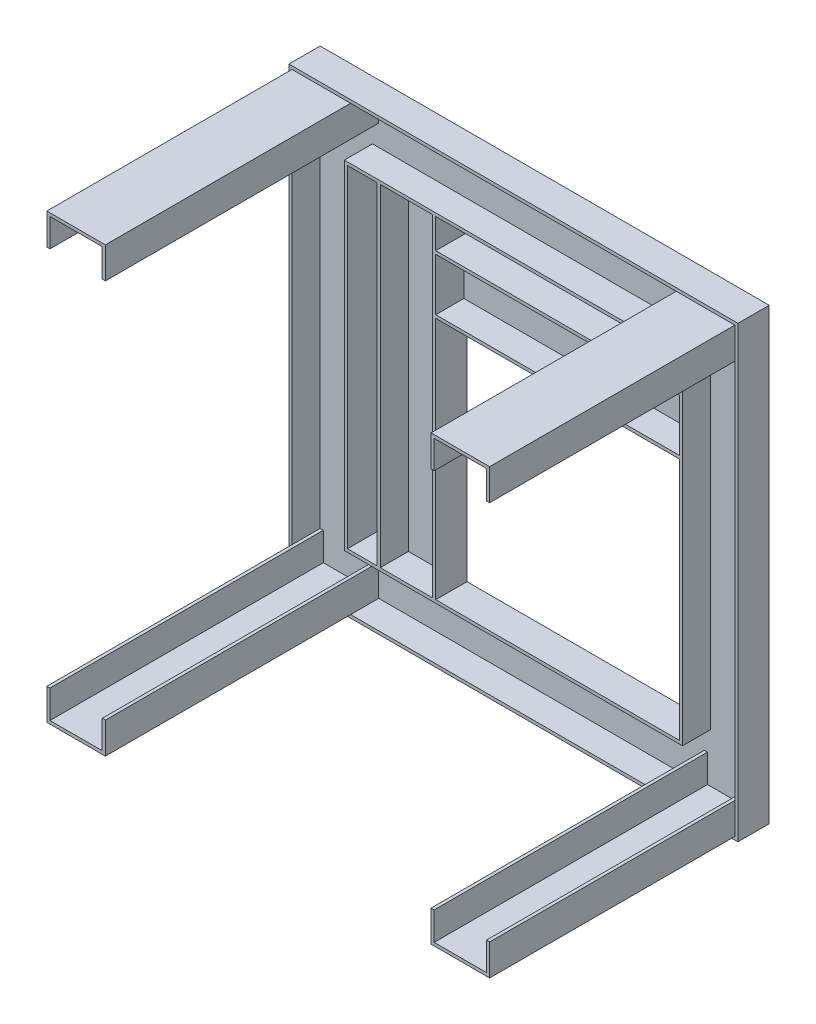
SolidWorks part; units mm, degrees
ref_plane "Front Plane" through (0, 0, 0) normal (0, 0, 1) x (1, 0, 0)
ref_plane "Top Plane" through (0, 0, 0) normal (0, 1, 0) x (1, 0, 0)
ref_plane "Right Plane" through (0, 0, 0) normal (1, 0, 0) x (0, 0, -1)
sketch "Sketch1" plane through (0, 0, 0) normal (0, 0, 1) x (1, 0, 0)
  line L1 (-250, -250) -> (250, -250)
  line L2 (-250, -250) -> (-250, 250)
  line L3 (-250, 250) -> (250, 250)
  line L4 (250, -250) -> (250, 250)
  line L5 (-250, -250) -> (250, 250) construction
  line L6 (-250, 250) -> (250, -250) construction
  point P0 (0, 0)
  dimension "D1" = 500
ref_plane "Plane1" through (0, -250, 0) normal (0, 1, 0) x (1, 0, 0)
sketch "Sketch2" plane through (0, -250, 0) normal (0, 1, 0) x (1, 0, 0)
  line L0 (250, 2) -> (250, -2) construction
  line L1 (212.5, 2) -> (287.5, 2)
  line L2 (287.5, 2) -> (287.5, -38)
  line L3 (287.5, -38) -> (283.5, -38)
  line L4 (283.5, -38) -> (283.5, -2)
  line L5 (283.5, -2) -> (216.5, -2)
  line L6 (-250, 0) -> (250, 0) construction
  line L7 (212.5, -38) -> (216.5, -38)
  line L8 (216.5, -38) -> (216.5, -2)
  line L9 (212.5, 2) -> (212.5, -38)
  point P13 (250, -2)
  dimension "D1" = 37.5
  dimension "D2" = 40
  dimension "D3" = 4
  dimension "D4" = 4
  dimension "D5" = 2
sweep "Sweep1" add profiles "Sketch2" path "Sketch1"
sketch "Sketch4" plane through (0, 0, 0) normal (0, 0, 1) x (1, 0, 0)
  line L0 (-137, 212.5) -> (-137, -212.5)
  line L1 (212.5, 212.5) -> (-212.5, 212.5) construction
  line L2 (-212.5, -212.5) -> (212.5, -212.5) construction
  line L3 (-212.5, 212.5) -> (-212.5, -212.5) construction
  dimension "D1" = 75.5
sketch "Sketch5" plane through (0, -212.5, 0) normal (0, 1, 0) x (1, 0, 0)
  line L0 (-137, 2) -> (-137, -38) construction
  line L1 (-212.5, 2) -> (212.5, 2) construction
  line L2 (-212.5, -38) -> (212.5, -38) construction
  line L3 (-174.5, 2) -> (-99.5, 2)
  line L4 (-99.5, 2) -> (-99.5, -38)
  line L5 (-99.5, -38) -> (-103.5, -38)
  line L6 (-103.5, -38) -> (-103.5, -2)
  line L7 (-103.5, -2) -> (-170.5, -2)
  line L8 (-170.5, -38) -> (-170.5, -2)
  line L9 (-174.5, -38) -> (-170.5, -38)
  line L10 (-174.5, 2) -> (-174.5, -38)
  point P13 (-137, -2)
  dimension "D1" = 37.5
  dimension "D2" = 4
  dimension "4" = 4
sweep "Sweep3" add profiles "Sketch5" path "Sketch4"
sketch "Sketch6" plane through (0, 0, 0) normal (0, 0, 1) x (1, 0, 0)
  line L0 (212.5, 137) -> (-99.5, 137)
  line L1 (212.5, 212.5) -> (212.5, -212.5) construction
  line L2 (-99.5, 212.5) -> (-99.5, -212.5) construction
  line L3 (212.5, 212.5) -> (-99.5, 212.5) construction
  dimension "D1" = 75.5
sketch "Sketch7" plane through (212.5, 0, 0) normal (-1, 0, 0) x (0, 0, 1)
  line L0 (-2, 137) -> (38, 137) construction
  line L1 (-2, 212.5) -> (-2, -212.5) construction
  line L2 (38, 212.5) -> (38, -212.5) construction
  line L3 (-2, 99.5) -> (-2, 174.5)
  line L4 (-2, 174.5) -> (38, 174.5)
  line L5 (38, 174.5) -> (38, 170.5)
  line L6 (38, 170.5) -> (2, 170.5)
  line L7 (2, 170.5) -> (2, 103.5)
  line L8 (38, 103.5) -> (2, 103.5)
  line L9 (38, 99.5) -> (38, 103.5)
  line L10 (-2, 99.5) -> (38, 99.5)
  point P13 (2, 137)
  dimension "D1" = 37.5
  dimension "D2" = 4
  dimension "D3" = 4
sweep "Sweep4" add profiles "Sketch7" path "Sketch6"
sketch "Sketch8" plane through (0, 0, 2) normal (0, 0, 1) x (1, 0, 0)
  line L0 (-246, 283.5) -> (-246, 268.2683) construction
  line L1 (-283.5, 283.5) -> (-208.5, 283.5)
  line L2 (-208.5, 283.5) -> (-208.5, 243.5)
  line L3 (-208.5, 243.5) -> (-212.5, 243.5)
  line L4 (-212.5, 243.5) -> (-212.5, 279.5)
  line L5 (-212.5, 279.5) -> (-279.5, 279.5)
  line L6 (283.5, 283.5) -> (-283.5, 283.5) construction
  line L7 (-279.5, 243.5) -> (-279.5, 279.5)
  line L8 (-283.5, 243.5) -> (-279.5, 243.5)
  line L9 (-283.5, 283.5) -> (-283.5, 243.5)
  line L10 (-283.5, 283.5) -> (-283.5, -283.5) construction
  point P10 (-246, 279.5)
  dimension "D1" = 37.5
  dimension "D2" = 40
  dimension "D3" = 4
  dimension "D4" = 4
extrude "Boss-Extrude1" add sketch "Sketch8" along normal blind 350
ref_axis "Axis1" through (0, 0, 0) along (0, 0, -1)
pattern_linear "LPattern1" count 2 spacing 492 along (1, 0, 0) of "Boss-Extrude1"
mirror "Mirror1" about plane through (0, 0, 0) normal (0, 1, 0) of "LPattern1"
